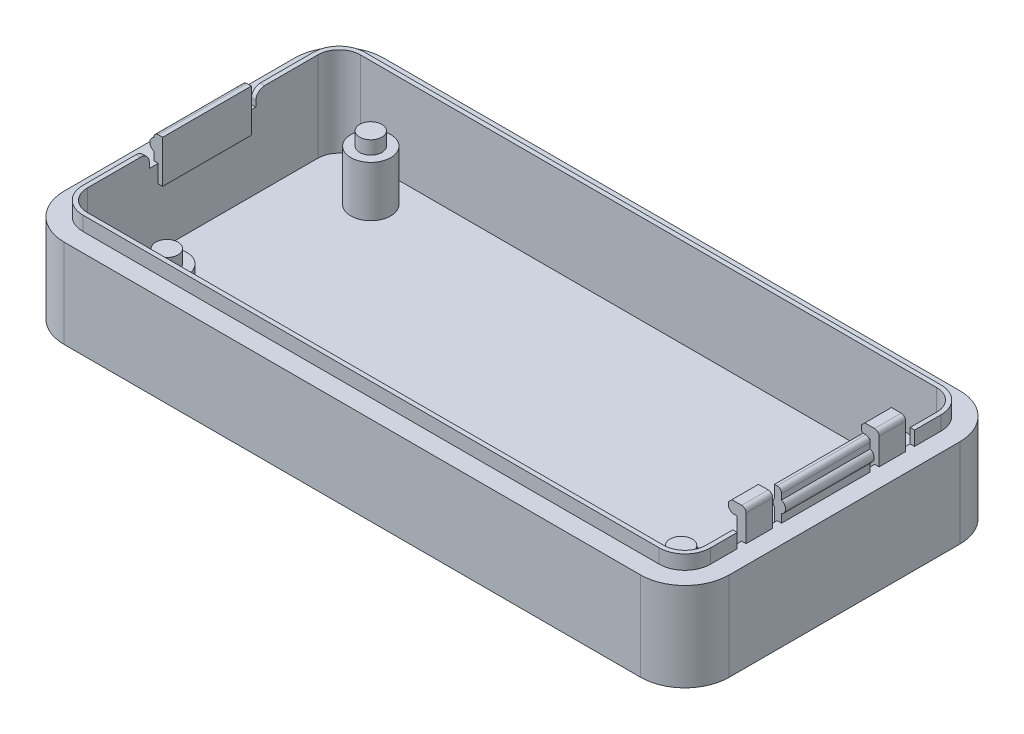
SolidWorks part; units mm, degrees
ref_plane "前视基准面" through (0, 0, 0) normal (0, 0, 1) x (1, 0, 0)
ref_plane "上视基准面" through (0, 0, 0) normal (0, 1, 0) x (1, 0, 0)
ref_plane "右视基准面" through (0, 0, 0) normal (1, 0, 0) x (0, 0, -1)
sketch "zero" plane through (0, 0, 0) normal (0, 1, 0) x (1, 0, 0)
  line L1 (-29.5, 15) -> (29.5, 15)
  line L2 (-32.5, 12) -> (-32.5, -12)
  line L3 (-29.5, -15) -> (29.5, -15)
  line L4 (32.5, 12) -> (32.5, -12)
  line L5 (-32.5, 15) -> (32.5, -15) construction
  line L6 (-32.5, -15) -> (32.5, 15) construction
  line L7 (-25.7, -15) -> (-14.5, -15)
  line L8 (-25.7, -15) -> (-25.7, -9.6569)
  line L9 (-25.7, -9.6569) -> (-14.5, -9.6569)
  line L10 (-14.5, -15) -> (-14.5, -9.6569)
  line L11 (5.2, -15) -> (12.7, -15)
  line L12 (5.2, -15) -> (5.2, -11)
  line L13 (5.2, -11) -> (12.7, -11)
  line L14 (12.7, -15) -> (12.7, -11)
  line L15 (17.8, -15) -> (25.3, -15)
  line L16 (17.8, -15) -> (17.8, -11)
  line L17 (17.8, -11) -> (25.3, -11)
  line L18 (25.3, -15) -> (25.3, -11)
  line L19 (-32.5, 7.7) -> (-19.5, 7.7)
  line L20 (-32.5, 7.7) -> (-32.5, -4.3)
  line L21 (-32.5, -4.3) -> (-19.5, -4.3)
  line L22 (-19.5, 7.7) -> (-19.5, -4.3)
  line L23 (-25.5, 14) -> (25.5, 14)
  line L24 (-25.5, 14) -> (-25.5, 8.8)
  line L25 (-25.5, 8.8) -> (25.5, 8.8)
  line L26 (25.5, 14) -> (25.5, 8.8)
  line L27 (-19.5, 7.2329) -> (-35.5, 7.2329)
  line L28 (-19.5, 7.2329) -> (-19.5, -3.7671)
  line L29 (-19.5, -3.7671) -> (-35.5, -3.7671)
  line L30 (-35.5, 7.2329) -> (-35.5, -3.7671)
  arc A0 (29.5, -15) -> (32.5, -12) centre (29.5, -12) ccw
  arc A1 (29.5, 15) -> (32.5, 12) centre (29.5, 12) cw
  arc A2 (-32.5, -12) -> (-29.5, -15) centre (-29.5, -12) ccw
  arc A3 (-29.5, 15) -> (-32.5, 12) centre (-29.5, 12) ccw
  circle A4 centre (-29, 11.4) radius 3
  circle A5 centre (-29, -11.5) radius 3
  circle A6 centre (29, 11.4) radius 3
  circle A7 centre (29, -11.5) radius 3
  circle A8 centre (-29, 11.4) radius 1.375
  circle A9 centre (-29, -11.5) radius 1.375
  circle A10 centre (29, -11.5) radius 1.375
  circle A11 centre (29, 11.4) radius 1.375
  point P0 (0, 0)
  dimension "D3" = 3
  dimension "D4" = 6
  dimension "D9" = 2.75
  dimension "D1" = 65
  dimension "D2" = 30
  dimension "D5" = 3.6
  dimension "D6" = 3.5
  dimension "D7" = 3.5
  dimension "D8" = 3.5
  dimension "D10" = 12
  dimension "D11" = 7.3
  dimension "D12" = 13
  dimension "D13" = 11.2
  dimension "D14" = 6.8
  dimension "D15" = 19.7
  dimension "D16" = 7.5
  dimension "D17" = 7.5
  dimension "D18" = 5.1
  dimension "D19" = 4
  dimension "D20" = 5.2
  dimension "D21" = 7
  dimension "D22" = 7
  dimension "D23" = 1
  dimension "D24" = 11
  dimension "D25" = 16
sketch "sugar" plane through (0, 0, 0) normal (0, 1, 0) x (1, 0, 0)
  line L1 (-29.5, 15) -> (29.5, 15)
  line L2 (-32.5, 12) -> (-32.5, -12)
  line L3 (-29.5, -15) -> (29.5, -15)
  line L4 (32.5, 12) -> (32.5, -12)
  line L5 (-32.5, 15) -> (32.5, -15) construction
  line L6 (-32.5, -15) -> (32.5, 15) construction
  line L7 (23.5, -11.5) -> (19.5, -11.5)
  line L8 (23.5, -11.5) -> (23.5, -13.9082)
  line L9 (23.5, -13.9082) -> (19.5, -13.9082)
  line L10 (19.5, -11.5) -> (19.5, -13.9082)
  line L11 (16, -11.0071) -> (8.5, -11.0071)
  line L12 (16, -11.0071) -> (16, -15)
  line L13 (16, -15) -> (8.5, -15)
  line L14 (8.5, -11.0071) -> (8.5, -15)
  line L15 (20.5, -13.9082) -> (22.5, -13.9082)
  line L16 (20.5, -13.9082) -> (20.5, -14.8173)
  line L17 (20.5, -14.8173) -> (22.5, -14.8173)
  line L18 (22.5, -13.9082) -> (22.5, -14.8173)
  arc A0 (29.5, 15) -> (32.5, 12) centre (29.5, 12) cw
  arc A1 (29.5, -15) -> (32.5, -12) centre (29.5, -12) ccw
  arc A2 (-32.5, -12) -> (-29.5, -15) centre (-29.5, -12) ccw
  arc A3 (-29.5, 15) -> (-32.5, 12) centre (-29.5, 12) ccw
  circle A4 centre (-29, 11.4) radius 3
  circle A5 centre (-29, 11.4) radius 1.375
  circle A6 centre (-29, -11.5) radius 3
  circle A7 centre (-29, -11.5) radius 1.375
  circle A8 centre (29, 11.4) radius 3
  circle A9 centre (29, 11.4) radius 1.375
  circle A10 centre (29, -11.5) radius 3
  circle A11 centre (29, -11.5) radius 1.375
  dimension "D3" = 3
  dimension "D1" = 65
  dimension "D2" = 30
  dimension "D4" = 9
  dimension "D5" = 4
  dimension "D6" = 3.5
  dimension "D7" = 7.5
  dimension "D8" = 2
  dimension "D9" = 1
sketch "case" plane through (0, 0, 0) normal (0, 1, 0) x (1, 0, 0)
  line L1 (-34.0422, 18) -> (30.9578, 18)
  line L2 (-39.0422, 13) -> (-39.0422, -13)
  line L3 (-34.0422, -18) -> (30.9578, -18)
  line L4 (35.9578, 13) -> (35.9578, -13)
  line L5 (-39.0422, 18) -> (35.9578, -18) construction
  line L6 (-39.0422, -18) -> (35.9578, 18) construction
  arc A0 (-39.0422, -13) -> (-34.0422, -18) centre (-34.0422, -13) ccw
  arc A1 (30.9578, -18) -> (35.9578, -13) centre (30.9578, -13) ccw
  arc A2 (30.9578, 18) -> (35.9578, 13) centre (30.9578, 13) cw
  arc A3 (-34.0422, 18) -> (-39.0422, 13) centre (-34.0422, 13) ccw
  point P0 (-1.5422, 0)
  point P3 (-1.5422, 0)
  dimension "D3" = 5
  dimension "D1" = 75
  dimension "D2" = 36
extrude "凸台-拉伸2" add sketch "case" along normal blind 10
sketch "草图2" plane through (0, 0, 0) normal (0, 1, 0) x (1, 0, 0)
  line L4 (-34.0422, -15.4) -> (30.9578, -15.4)
  line L5 (33.3578, -13) -> (33.3578, 13)
  line L6 (30.9578, 15.4) -> (-34.0422, 15.4)
  line L7 (-36.4422, 13) -> (-36.4422, -13)
  line L8 (33.8578, -13) -> (33.8578, 13)
  line L9 (30.9578, 15.9) -> (-34.0422, 15.9)
  line L10 (-36.9422, 13) -> (-36.9422, -13)
  line L11 (-34.0422, -15.9) -> (30.9578, -15.9)
  line L12 (33.8578, -13) -> (33.8578, 13)
  line L13 (30.9578, 15.9) -> (-34.0422, 15.9)
  line L14 (-36.9422, 13) -> (-36.9422, -13)
  line L15 (-34.0422, -15.9) -> (30.9578, -15.9)
  arc A4 (30.9578, -15.4) -> (33.3578, -13) centre (30.9578, -13) ccw
  arc A5 (33.3578, 13) -> (30.9578, 15.4) centre (30.9578, 13) ccw
  arc A6 (-34.0422, 15.4) -> (-36.4422, 13) centre (-34.0422, 13) ccw
  arc A7 (-36.4422, -13) -> (-34.0422, -15.4) centre (-34.0422, -13) ccw
  arc A8 (30.9578, -15.9) -> (33.8578, -13) centre (30.9578, -13) ccw
  arc A9 (33.8578, 13) -> (30.9578, 15.9) centre (30.9578, 13) ccw
  arc A10 (-34.0422, 15.9) -> (-36.9422, 13) centre (-34.0422, 13) ccw
  arc A11 (-36.9422, -13) -> (-34.0422, -15.9) centre (-34.0422, -13) ccw
  arc A12 (30.9578, -15.9) -> (33.8578, -13) centre (30.9578, -13) ccw
  arc A13 (33.8578, 13) -> (30.9578, 15.9) centre (30.9578, 13) ccw
  arc A14 (-34.0422, 15.9) -> (-36.9422, 13) centre (-34.0422, 13) ccw
  arc A15 (-36.9422, -13) -> (-34.0422, -15.9) centre (-34.0422, -13) ccw
  dimension "D1" = 2.1
  dimension "D2" = 0.5
ref_plane "基准面1" through (0, 10, 0) normal (0, 1, 0) x (1, 0, 0)
sketch "草图3" plane through (0, 10, 0) normal (0, 1, 0) x (1, 0, 0)
  line L4 (-34.0422, -15.4) -> (30.9578, -15.4)
  line L5 (33.3578, -13) -> (33.3578, 13)
  line L6 (30.9578, 15.4) -> (-34.0422, 15.4)
  line L7 (-36.4422, 13) -> (-36.4422, -13)
  line L8 (-34.0422, -15.4) -> (30.9578, -15.4)
  line L9 (33.3578, -13) -> (33.3578, 13)
  line L10 (30.9578, 15.4) -> (-34.0422, 15.4)
  line L11 (-36.4422, 13) -> (-36.4422, -13)
  line L12 (-36.9422, 13) -> (-36.9422, -13)
  line L13 (-34.0422, -15.9) -> (30.9578, -15.9)
  line L14 (33.8578, -13) -> (33.8578, 13)
  line L15 (30.9578, 15.9) -> (-34.0422, 15.9)
  line L16 (-36.9422, 13) -> (-36.9422, -13)
  line L17 (-34.0422, -15.9) -> (30.9578, -15.9)
  line L18 (33.8578, -13) -> (33.8578, 13)
  line L19 (30.9578, 15.9) -> (-34.0422, 15.9)
  arc A4 (30.9578, -15.4) -> (33.3578, -13) centre (30.9578, -13) ccw
  arc A5 (33.3578, 13) -> (30.9578, 15.4) centre (30.9578, 13) ccw
  arc A6 (-34.0422, 15.4) -> (-36.4422, 13) centre (-34.0422, 13) ccw
  arc A7 (-36.4422, -13) -> (-34.0422, -15.4) centre (-34.0422, -13) ccw
  arc A8 (30.9578, -15.4) -> (33.3578, -13) centre (30.9578, -13) ccw
  arc A9 (33.3578, 13) -> (30.9578, 15.4) centre (30.9578, 13) ccw
  arc A10 (-34.0422, 15.4) -> (-36.4422, 13) centre (-34.0422, 13) ccw
  arc A11 (-36.4422, -13) -> (-34.0422, -15.4) centre (-34.0422, -13) ccw
  arc A12 (-36.9422, -13) -> (-34.0422, -15.9) centre (-34.0422, -13) ccw
  arc A13 (30.9578, -15.9) -> (33.8578, -13) centre (30.9578, -13) ccw
  arc A14 (33.8578, 13) -> (30.9578, 15.9) centre (30.9578, 13) ccw
  arc A15 (-34.0422, 15.9) -> (-36.9422, 13) centre (-34.0422, 13) ccw
  arc A16 (-36.9422, -13) -> (-34.0422, -15.9) centre (-34.0422, -13) ccw
  arc A17 (30.9578, -15.9) -> (33.8578, -13) centre (30.9578, -13) ccw
  arc A18 (33.8578, 13) -> (30.9578, 15.9) centre (30.9578, 13) ccw
  arc A19 (-34.0422, 15.9) -> (-36.9422, 13) centre (-34.0422, 13) ccw
  dimension "D1" = 0
  dimension "D2" = 0
extrude "凸台-拉伸4" add sketch "草图3" along normal blind 1.6
sketch "草图5" plane through (0, 10, 0) normal (0, 1, 0) x (1, 0, 0)
  line L0 (33.3578, -13) -> (33.3578, 13) construction
  line L1 (33.0578, 5) -> (33.3578, 5)
  line L2 (33.0578, 5) -> (33.0578, -5)
  line L3 (33.0578, -5) -> (33.3578, -5)
  line L4 (33.3578, 5) -> (33.3578, -5)
  line L5 (33.0578, 5) -> (33.3578, -5) construction
  line L6 (33.0578, -5) -> (33.3578, 5) construction
  point P0 (33.2078, 0)
  dimension "D2" = 10
  dimension "D3" = 0.3
  dimension "D4" = 0
ref_plane "基准面3" through (33.8578, 0, 0) normal (1, 0, 0) x (0, 0, -1)
sketch "草图7" plane through (0, 10, 0) normal (0, 1, 0) x (1, 0, 0)
  line L0 (-36.9422, 13) -> (-36.9422, -13) construction
  line L1 (-36.9422, 5) -> (-36.4422, 5)
  line L2 (-36.9422, 5) -> (-36.9422, -5)
  line L3 (-36.9422, -5) -> (-36.4422, -5)
  line L4 (-36.4422, 5) -> (-36.4422, -5)
  line L5 (-36.4422, 13) -> (-36.4422, -13) construction
  point P10 (-36.4422, 0)
  dimension "D1" = 5
  dimension "D2" = 10
extrude "凸台-拉伸8" add sketch "草图7" along normal blind 2.8
ref_plane "基准面5" through (0, 0, 5) normal (0, 0, 1) x (1, 0, 0)
sketch "草图8" plane through (0, 0, 5) normal (0, 0, 1) x (1, 0, 0)
  line L0 (-34.0422, 10) -> (-39.0422, 10) construction
  line L1 (-36.9422, 12.8) -> (-36.9422, 11.6) construction
  circle A0 centre (-36.6922, 11.6) radius 0.7
  dimension "D1" = 1.4
  dimension "D2" = 1.6
  dimension "D3" = 0.25
extrude "凸台-拉伸9" add sketch "草图8" against normal blind 10
fillet "圆角1" radius 0.5 1 edges at (-36.9422, 12.8, 0)
ref_plane "基准面7" through (-36.9422, 0, 0) normal (-1, 0, 0) x (0, 0, 1)
sketch "草图11" plane through (-36.9422, 0, 0) normal (-1, 0, 0) x (0, 0, 1)
  line L0 (-13, 10) -> (13, 10) construction
  line L1 (5, 11.6) -> (6, 11.6)
  line L2 (5, 11.6) -> (5, 10)
  line L3 (5, 10) -> (6, 10)
  line L4 (6, 11.6) -> (6, 10)
  line L6 (-5, 11.6) -> (-6, 11.6)
  line L7 (-5, 11.6) -> (-5, 10)
  line L8 (-5, 10) -> (-6, 10)
  line L9 (-6, 11.6) -> (-6, 10)
  dimension "D1" = 1
  dimension "D2" = 1
extrude "切除-拉伸1" cut sketch "草图11" against normal blind 1.2
fillet "圆角2" radius 1 2 edges at (-36.6922, 11.6, 6) (-36.6922, 11.6, -6)
ref_plane "基准面8" through (0, 0, 0) normal (0, -1, 0) x (-1, 0, 0)
sketch "草图13" plane through (0, 10, 0) normal (0, 1, 0) x (1, 0, 0)
  line L1 (-36.4422, -5) -> (-35.9422, -5)
  line L2 (-36.4422, -5) -> (-36.4422, 5)
  line L3 (-36.4422, 5) -> (-35.9422, 5)
  line L4 (-35.9422, -5) -> (-35.9422, 5)
  dimension "D1" = 0.5
extrude "凸台-拉伸10" add sketch "草图13" along normal blind 2.8
sketch "草图14" plane through (0, 10, 0) normal (0, 1, 0) x (1, 0, 0)
  line L4 (-34.0422, -15.4) -> (30.9578, -15.4)
  line L5 (33.3578, -13) -> (33.3578, 13)
  line L6 (30.9578, 15.4) -> (-34.0422, 15.4)
  line L7 (-36.4422, 13) -> (-36.4422, -13)
  line L8 (-34.0422, -15.4) -> (30.9578, -15.4)
  line L9 (33.3578, -13) -> (33.3578, 13)
  line L10 (30.9578, 15.4) -> (-34.0422, 15.4)
  line L11 (-36.4422, 13) -> (-36.4422, -13)
  arc A4 (30.9578, -15.4) -> (33.3578, -13) centre (30.9578, -13) ccw
  arc A5 (33.3578, 13) -> (30.9578, 15.4) centre (30.9578, 13) ccw
  arc A6 (-34.0422, 15.4) -> (-36.4422, 13) centre (-34.0422, 13) ccw
  arc A7 (-36.4422, -13) -> (-34.0422, -15.4) centre (-34.0422, -13) ccw
  arc A8 (30.9578, -15.4) -> (33.3578, -13) centre (30.9578, -13) ccw
  arc A9 (33.3578, 13) -> (30.9578, 15.4) centre (30.9578, 13) ccw
  arc A10 (-34.0422, 15.4) -> (-36.4422, 13) centre (-34.0422, 13) ccw
  arc A11 (-36.4422, -13) -> (-34.0422, -15.4) centre (-34.0422, -13) ccw
  dimension "D1" = 0
extrude "切除-拉伸2" cut sketch "草图14" against normal blind 8.5
extrude "凸台-拉伸11" add sketch "草图13<2>" against normal blind 2
sketch "草图13<2>" plane through (0, 10, 0) normal (0, 1, 0) x (1, 0, 0) same geometry as "草图13"
extrude "凸台-拉伸12" add sketch "草图5" against normal blind 2 and the other way blind 1.6
sketch "草图15" plane through (0, 1.5, 0) normal (0, 1, 0) x (1, 0, 0)
  line L1 (35.9578, -13) -> (35.9578, 13) construction
  line L5 (-39.0422, 13) -> (-39.0422, -13) construction
  line L6 (-34.0422, -18) -> (30.9578, -18) construction
  line L7 (30.9578, 18) -> (-34.0422, 18) construction
  circle A0 centre (29.0603, -11.5295) radius 2.25
  circle A1 centre (-28.9397, -11.5295) radius 2.25
  circle A2 centre (29.0603, 11.4705) radius 2.25
  circle A3 centre (-28.9397, 11.4705) radius 2.25
  point P2 (0, 0)
  point P11 (0, 0)
  dimension "D1" = 4.5
  dimension "D2" = 6.8975
  dimension "D3" = 10.1025
  dimension "D4" = 6.4705
  dimension "D5" = 6.5295
extrude "凸台-拉伸13" add sketch "草图15" along normal blind 5.7
sketch "草图16" plane through (0, 7.2, 0) normal (0, 1, 0) x (1, 0, 0)
  circle A0 centre (29.0603, -11.5295) radius 1.25
  circle A1 centre (29.0603, 11.4705) radius 1.25
  circle A2 centre (-28.9397, -11.5295) radius 1.25
  circle A3 centre (-28.9397, 11.4705) radius 1.25
  dimension "D1" = 2.5
extrude "凸台-拉伸14" add sketch "草图16" along normal blind 1.5
sketch "草图17" plane through (0, 11.6, 0) normal (0, 1, 0) x (1, 0, 0)
  line L0 (33.3578, -13) -> (33.3578, -5) construction
  line L1 (33.3578, -5) -> (33.8578, -5)
  line L2 (33.3578, -5) -> (33.3578, -6)
  line L3 (33.3578, -6) -> (33.8578, -6)
  line L4 (33.8578, -5) -> (33.8578, -6)
  line L5 (33.3578, -13) -> (33.3578, 13) construction
  line L6 (33.8578, -13) -> (33.8578, 13) construction
  line L8 (33.3578, 5) -> (33.8578, 5)
  line L9 (33.3578, 5) -> (33.3578, 6)
  line L10 (33.3578, 6) -> (33.8578, 6)
  line L11 (33.8578, 5) -> (33.8578, 6)
  dimension "D1" = 1
  dimension "D2" = 1
extrude "切除-拉伸3" cut sketch "草图17" against normal blind 1.6
sketch "草图19" plane through (0, 11.6, 0) normal (0, 1, 0) x (1, 0, 0)
  line L0 (33.0578, 5) -> (33.0578, -5) construction
  line L1 (33.8578, -5) -> (33.0578, -5)
  line L2 (33.8578, -5) -> (33.8578, 5)
  line L3 (33.8578, 5) -> (33.0578, 5)
  line L4 (33.0578, -5) -> (33.0578, 5)
extrude "凸台-拉伸15" add sketch "草图19" along normal blind 1.8
sketch "草图20" plane through (0, 0, -5) normal (0, 0, -1) x (-1, 0, 0)
  line L0 (-30.9578, 10) -> (-35.9578, 10) construction
  line L3 (-33.8578, 10) -> (-33.8578, 13.4) construction
  circle A0 centre (-33.6078, 11.6) radius 0.7
  dimension "D1" = 1.4
  dimension "D2" = 1.6
  dimension "D3" = 0.25
extrude "凸台-拉伸16" add sketch "草图20" against normal blind 10
fillet "圆角4" radius 0.5 1 edges at (33.8578, 13.4, 0)
sketch "草图21" plane through (0, 11.6, 0) normal (0, 1, 0) x (1, 0, 0)
  line L1 (33.3578, -6) -> (33.8578, -6)
  line L2 (33.3578, -6) -> (33.3578, -9)
  line L3 (33.3578, -9) -> (33.8578, -9)
  line L4 (33.8578, -6) -> (33.8578, -9)
  line L6 (33.3578, 6) -> (33.8578, 6)
  line L7 (33.3578, 6) -> (33.3578, 9)
  line L8 (33.3578, 9) -> (33.8578, 9)
  line L9 (33.8578, 6) -> (33.8578, 9)
  dimension "D1" = 3
  dimension "D2" = 3
extrude "凸台-拉伸17" add sketch "草图21" along normal blind 1.9
sketch "草图22" plane through (33.3578, 0, 0) normal (-1, 0, 0) x (0, 0, 1)
  line L0 (-6, 10) -> (-6, 13.5) construction
  line L1 (-9, 13.5) -> (-6, 13.5)
  line L2 (-9, 13.5) -> (-9, 7.2)
  line L3 (-9, 7.2) -> (-6, 7.2)
  line L4 (-6, 13.5) -> (-6, 7.2)
  line L5 (9, 13.5) -> (9, 11.6) construction
  line L6 (6, 13.5) -> (9, 13.5)
  line L7 (6, 13.5) -> (6, 7.2)
  line L8 (6, 7.2) -> (9, 7.2)
  line L9 (9, 13.5) -> (9, 7.2)
  dimension "D1" = 6.3
extrude "凸台-拉伸23" add sketch "草图22" along normal blind 0.5
fillet "圆角12" radius 0.5 2 edges at (33.8578, 13.5, -7.5) (33.8578, 13.5, 7.5)
sketch "草图29" plane through (0, 11.6, 0) normal (0, 1, 0) x (1, 0, 0)
  line L1 (33.3578, -9) -> (33.8578, -9)
  line L2 (33.3578, -9) -> (33.3578, -10)
  line L3 (33.3578, -10) -> (33.8578, -10)
  line L4 (33.8578, -9) -> (33.8578, -10)
  line L5 (33.3578, -13) -> (33.3578, 13) construction
  line L6 (33.8578, 9) -> (33.3578, 9)
  line L7 (33.8578, 9) -> (33.8578, 10)
  line L8 (33.8578, 10) -> (33.3578, 10)
  line L9 (33.3578, 9) -> (33.3578, 10)
  dimension "D1" = 1
  dimension "D2" = 1
extrude "切除-拉伸5" cut sketch "草图29" against normal blind 1.6
sketch "草图30" plane through (32.8578, 0, 0) normal (-1, 0, 0) x (0, 0, 1)
  line L0 (9, 7.2) -> (9, 13.5) construction
  line L1 (6, 13.5) -> (9, 13.5)
  line L2 (6, 13.5) -> (6, 12.2)
  line L3 (6, 12.2) -> (9, 12.2)
  line L4 (9, 13.5) -> (9, 12.2)
  line L5 (-6, 7.2) -> (-6, 13.5) construction
  line L6 (-9, 13.5) -> (-6, 13.5)
  line L7 (-9, 13.5) -> (-9, 12.2)
  line L8 (-9, 12.2) -> (-6, 12.2)
  line L9 (-6, 13.5) -> (-6, 12.2)
  dimension "D1" = 1.3
extrude "凸台-拉伸26" add sketch "草图30" along normal blind 1
chamfer "倒角7" distance 0.4 angle 45 4 edges at (31.8578, 13.5, -7.5) (31.8578, 12.2, -7.5) (31.8578, 13.5, 7.5) (31.8578, 12.2, 7.5)
sketch "草图36" plane through (0, 0, 0) normal (0, -1, 0) x (1, 0, 0)
sketch_block_instance "块1-1"
sketch_block "块1"
